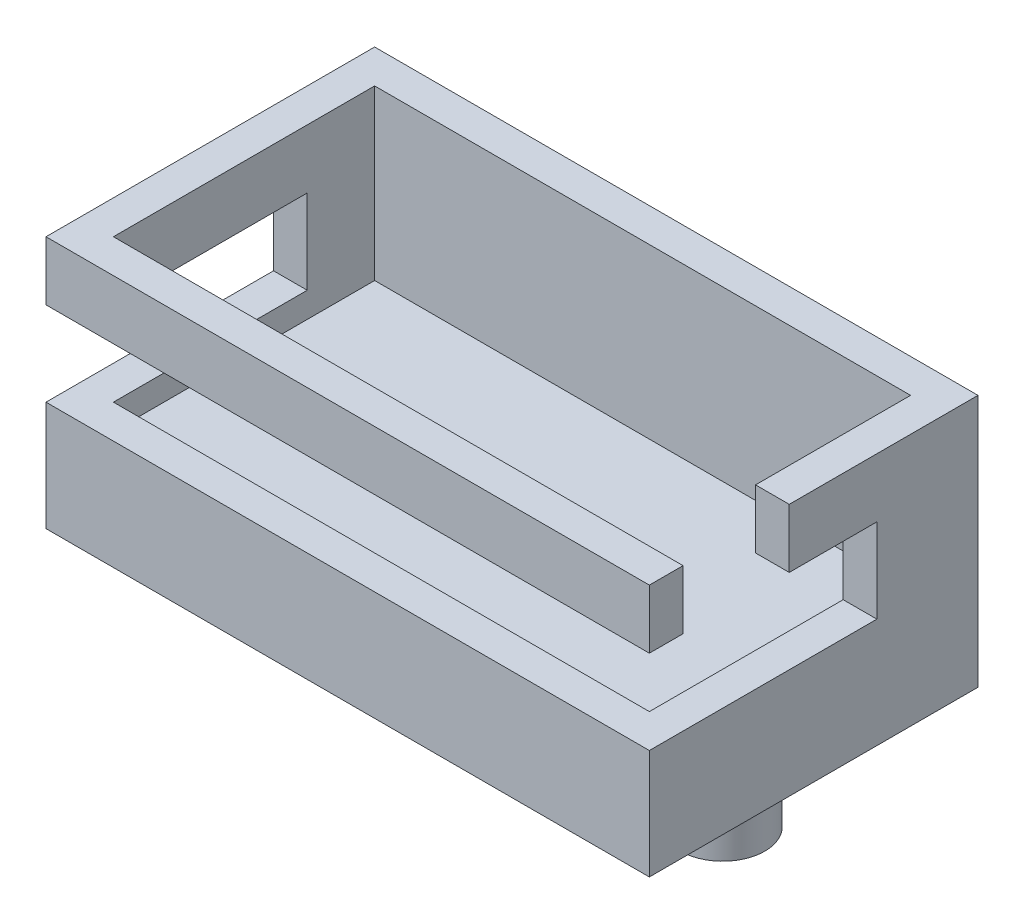
SolidWorks part; units mm, degrees
ref_plane "Front Plane" through (0, 0, 0) normal (0, 0, 1) x (1, 0, 0)
ref_plane "Top Plane" through (0, 0, 0) normal (0, 1, 0) x (1, 0, 0)
ref_plane "Right Plane" through (0, 0, 0) normal (1, 0, 0) x (0, 0, -1)
sketch "Sketch1" plane through (0, 0, 0) normal (0, 1, 0) x (1, 0, 0)
  line L0 (-2, -2) -> (-2, 17.5)
  line L1 (0, 0) -> (31.8, 0)
  line L2 (0, 0) -> (0, 15.5)
  line L3 (0, 15.5) -> (31.8, 15.5)
  line L4 (31.8, 0) -> (31.8, 15.5)
  line L5 (-2, 17.5) -> (33.8, 17.5)
  line L6 (33.8, -2) -> (33.8, 17.5)
  line L7 (-2, -2) -> (33.8, -2)
  dimension "D1" = 15.5
  dimension "D2" = 31.8
  dimension "D3" = 2
extrude "Boss-Extrude1" add sketch "Sketch1" along normal blind 10
extrude "Boss-Extrude2" add sketch "Sketch1<2>" against normal blind 5 contours L0 L7 L6 L5 L4 L1 L2 L3 | L1 L4 L3 L2 region at (-1.5923, 0, -7.75) region at (15.9, 0, -7.75)
sketch "Sketch1<2>" plane through (0, 0, 0) normal (0, 1, 0) x (1, 0, 0) same geometry as "Sketch1"
sketch "Sketch2" plane through (0, 0, 2) normal (0, 0, 1) x (1, 0, 0)
  line L0 (33.8, 10) -> (33.8, -5) construction
  line L1 (-2, 6.5) -> (33.8, 6.5)
  line L2 (-2, 6.5) -> (-2, 1.5)
  line L3 (-2, 1.5) -> (33.8, 1.5)
  line L4 (33.8, 6.5) -> (33.8, 1.5)
  line L5 (-2, -5) -> (33.8, -5) construction
  line L6 (-2, 10) -> (-2, -5) construction
  dimension "D2" = 5
  dimension "D3" = 6.5
extrude "Cut-Extrude1" cut sketch "Sketch2" against normal offset from surface (13.5 mm away) 6 up to face at (15.9, 2.5, -17.5)
sketch "Sketch3" plane through (33.8, 0, 0) normal (1, 0, 0) x (0, 0, -1)
  line L0 (-2, 10) -> (17.5, 10) construction
  line L1 (0, 6.5) -> (6.3, 6.5)
  line L2 (0, 6.5) -> (0, 10)
  line L3 (0, 10) -> (6.3, 10)
  line L4 (6.3, 6.5) -> (6.3, 10)
  line L6 (11.5, 6.5) -> (-2, 6.5) construction
  point P7 (0, 0)
  point P8 (0.2142, 7.7774)
  point P10 (0, 0)
  dimension "D1" = 6.3
extrude "Cut-Extrude2" cut sketch "Sketch3" against normal up to surface (2 mm away) up to face at (31.8, 4.5, -6.75)
sketch "Sketch4" plane through (0, -5, 0) normal (0, -1, 0) x (1, 0, 0)
  line L0 (15.9, 2) -> (15.9, -17.5) construction
  line L1 (-2, 2) -> (33.8, 2) construction
  line L2 (-2, -17.5) -> (33.8, -17.5) construction
  line L3 (3.4, -7.75) -> (15.9, -7.75) construction
  circle A0 centre (3.4, -7.75) radius 2.5
  circle A1 centre (28.4, -7.75) radius 2.5
  dimension "D1" = 5
  dimension "D2" = 12.5
extrude "Boss-Extrude3" add sketch "Sketch4" along normal blind 5
fillet "Fillet1" radius 0.4 2 edges at (28.4, -5, -5.25) (3.4, -5, -5.25)
